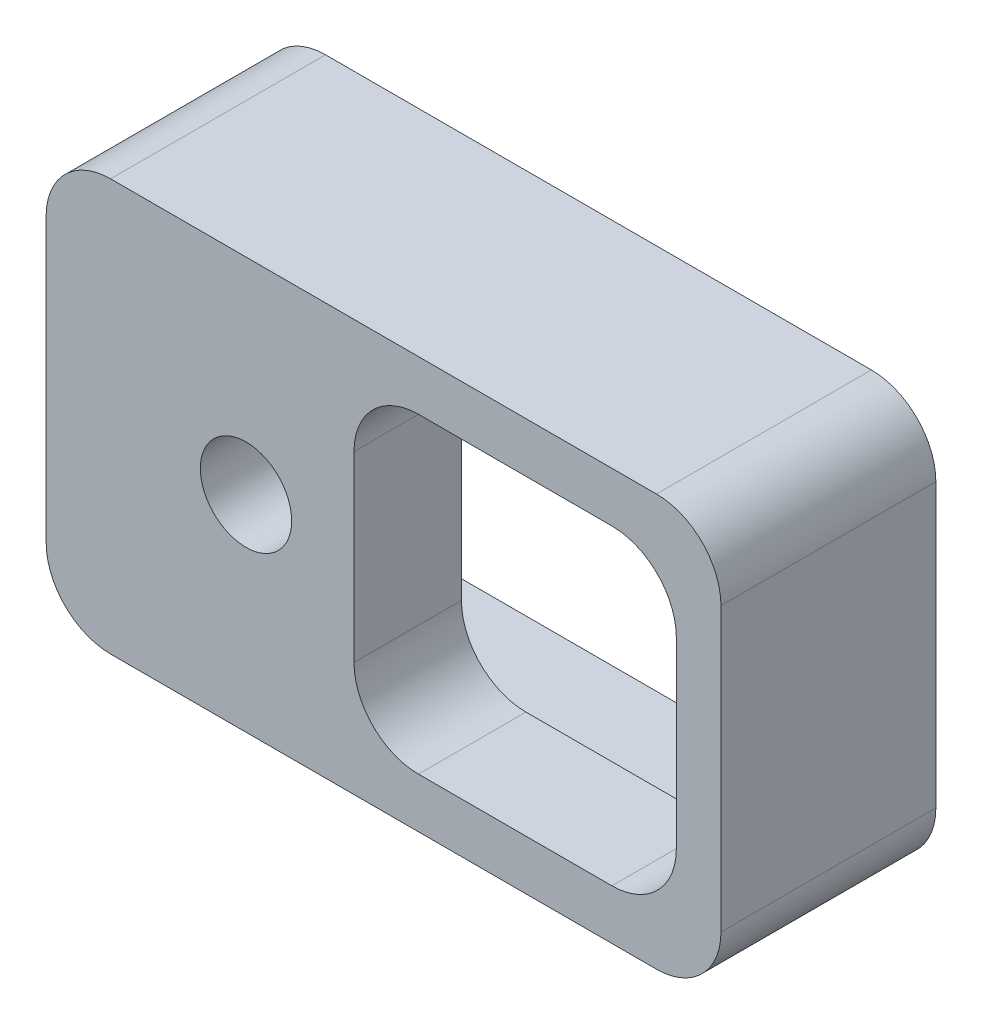
SolidWorks part; units mm, degrees
ref_plane "Front Plane" through (0, 0, 0) normal (0, 0, 1) x (1, 0, 0)
ref_plane "Top Plane" through (0, 0, 0) normal (0, 1, 0) x (1, 0, 0)
ref_plane "Right Plane" through (0, 0, 0) normal (1, 0, 0) x (0, 0, -1)
sketch "Sketch2" plane through (0, 0, 0) normal (0, 0, 1) x (1, 0, 0)
  line L1 (0, 0) -> (58, 0)
  line L2 (0, 0) -> (0, -33.5)
  line L3 (0, -33.5) -> (58, -33.5)
  line L4 (58, 0) -> (58, -33.5)
  line L5 (26.25, -2.25) -> (56.25, -2.25)
  line L6 (26.25, -2.25) -> (26.25, -31.25)
  line L7 (26.25, -31.25) -> (56.25, -31.25)
  line L8 (56.25, -2.25) -> (56.25, -31.25)
  line L9 (26.25, -2.25) -> (56.25, -31.25) construction
  line L10 (26.25, -31.25) -> (56.25, -2.25) construction
  line L11 (-2.4, 2.4) -> (60.4, 2.4)
  line L12 (-2.4, 2.4) -> (-2.4, -35.9)
  line L13 (-2.4, -35.9) -> (60.4, -35.9)
  line L14 (60.4, 2.4) -> (60.4, -35.9)
  circle A1 centre (16.2, -16.75) radius 4.25
  circle A2 centre (14.45, -16.75) radius 6
  circle A3 centre (14.45, -16.75) radius 6.5
  point P5 (41.25, -16.75)
  point P6 (41.25, -16.75)
  point P7 (16.2, -16.75)
  dimension "D9" = 8.5
  dimension "D10" = 12
  dimension "D15" = 13
  dimension "D1" = 33.5
  dimension "D2" = 58
  dimension "D3" = 16.75
  dimension "D4" = 16.75
  dimension "D5" = 16.2
  dimension "D6" = 16.75
  dimension "D7" = 30
  dimension "D8" = 29
  dimension "D11" = 2.4
  dimension "D12" = 2.4
  dimension "D13" = 2.4
  dimension "D14" = 2.4
extrude "Boss-Extrude1" add sketch "Sketch2" along normal blind 10 contours L14 L11 L12 L13 L1 L4 L3 L2 | L4 L1 L2 L3 A2 L5 L8 L7 L6 | A1 A2 | A3 A2 region at (29, -0.6698, 0) region at (29, 1.6644, 0) region at (8.6197, -16.75, 0) region at (8.1338, -16.75, 0)
extrude "Boss-Extrude2" add sketch "Sketch2<3>" against normal blind 10 contours L14 L11 L12 L13 L1 L4 L3 L2 region at (29, 1.6644, 0)
sketch "Sketch2<3>" plane through (0, 0, 0) normal (0, 0, 1) x (1, 0, 0) same geometry as "Sketch2"
extrude "Cut-Extrude1" cut sketch "Sketch2<4>" along normal blind 3 contours A3
sketch "Sketch2<4>" plane through (0, 0, 0) normal (0, 0, 1) x (1, 0, 0) same geometry as "Sketch2"
fillet "Fillet1" radius 3.6 4 edges at (58, -33.5, -5) (0, -33.5, -5) (0, 0, -5) (58, 0, -5)
fillet "Fillet2" radius 6 8 edges at (56.25, -31.25, 5) (26.25, -31.25, 5) (26.25, -2.25, 5) (56.25, -2.25, 5) (60.4, -35.9, 0) (-2.4, -35.9, 0) (-2.4, 2.4, 0) (60.4, 2.4, 0)
